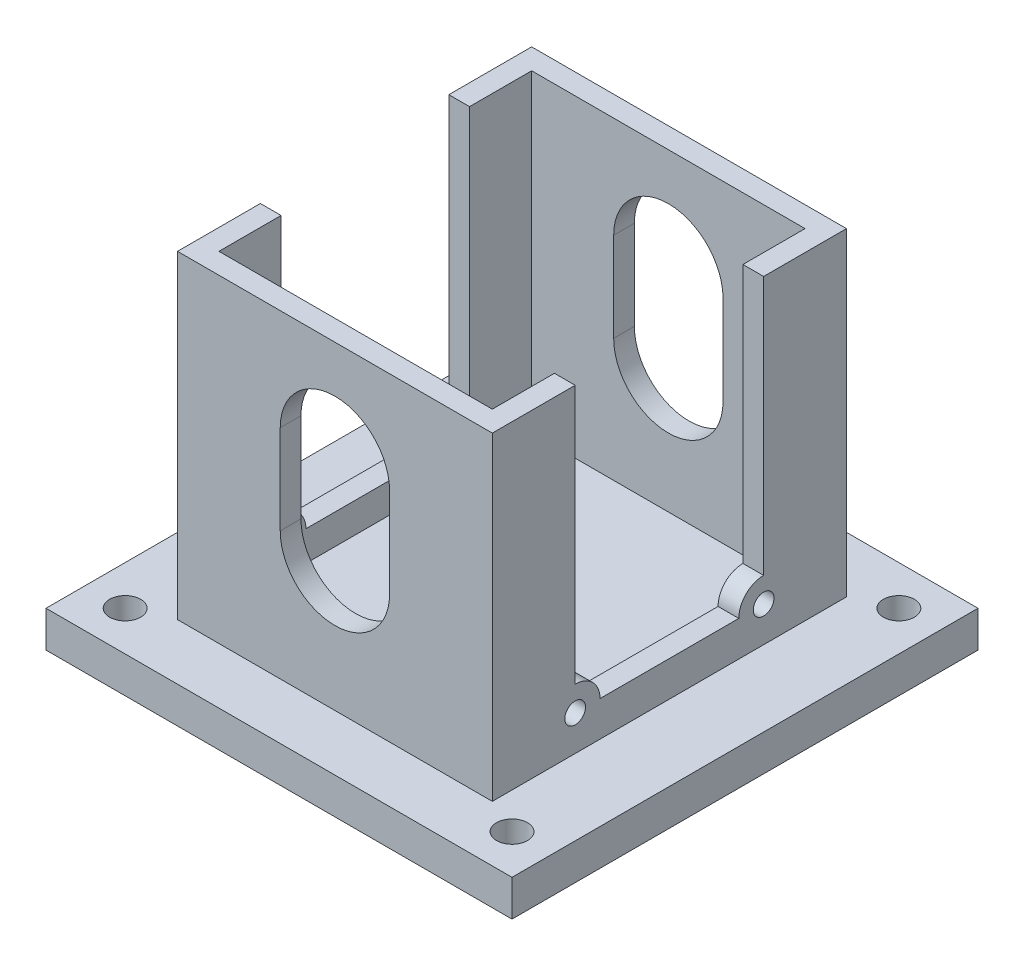
SolidWorks part; units mm, degrees
ref_plane "前视基准面" through (0, 0, 0) normal (0, 0, 1) x (1, 0, 0)
ref_plane "上视基准面" through (0, 0, 0) normal (0, 1, 0) x (1, 0, 0)
ref_plane "右视基准面" through (0, 0, 0) normal (1, 0, 0) x (0, 0, -1)
other "Configuration Table"
sketch "草图1" plane through (0, 0, 0) normal (1, 0, 0) x (0, 0, -1)
  line L0 (0, 0) -> (9.1, 0) construction
  line L1 (0, 0) -> (-9.1, 0) construction
  line L2 (-6.7, 0) -> (6.7, 0)
  line L3 (0, 0) -> (0, 14.2122) construction
  line L4 (-9.1, 0) -> (-10.1, 0) construction
  line L5 (-9.1, 0) -> (-9.1, -1) construction
  line L6 (-9.1, -4.9) -> (9.1, -4.9)
  line L7 (-17.1, 0) -> (-17.1, -4.9)
  line L8 (-17.1, -4.9) -> (-9.1, -4.9)
  line L9 (-9.1, 2.4) -> (-9.1, 27.4)
  line L10 (-9.1, 27.4) -> (-17.1, 27.4)
  line L11 (-17.1, 27.4) -> (-17.1, 0)
  line L12 (-11.5, 0) -> (-17.1, 0) construction
  line L13 (-9.1, -2.4) -> (-9.1, -4.9) construction
  line L14 (9.1, 27.4) -> (17.1, 27.4)
  line L15 (9.1, 2.4) -> (9.1, 27.4)
  line L16 (17.1, 0) -> (17.1, -4.9)
  line L17 (17.1, 27.4) -> (17.1, 0)
  line L18 (17.1, -4.9) -> (9.1, -4.9)
  circle A0 centre (9.1, 0) radius 1
  circle A1 centre (-9.1, 0) radius 1
  arc A2 (-6.7, 0) -> (-9.1, 2.4) centre (-9.1, 0) ccw
  arc A3 (6.7, 0) -> (9.1, 2.4) centre (9.1, 0) cw
  point P26 (0, -4.9)
  dimension "D3" = 2
  dimension "D4" = 2
  dimension "D5" = 4.8
  dimension "D1" = 9.1
  dimension "D6" = 8
  dimension "D7" = 4.9
  dimension "D8" = 25
extrude "凸台-拉伸1" add sketch "草图1" along normal blind 15.2 and the other way blind 15.2
sketch "草图2" plane through (0, 27.4, 0) normal (0, 1, 0) x (1, 0, 0)
  line L0 (-15.2, 17.1) -> (15.2, 17.1) construction
  line L1 (-13.2, 15.1) -> (13.2, 15.1)
  line L2 (-13.2, 15.1) -> (-13.2, -15.1)
  line L3 (-13.2, -15.1) -> (13.2, -15.1)
  line L4 (13.2, 15.1) -> (13.2, -15.1)
  line L5 (15.2, 17.1) -> (15.2, 9.1) construction
  line L6 (-15.2, 17.1) -> (-15.2, 9.1) construction
  line L7 (-15.2, -17.1) -> (15.2, -17.1) construction
  dimension "D1" = 2
  dimension "D2" = 2
  dimension "D3" = 2
  dimension "D4" = 2
extrude "切除-拉伸1" cut sketch "草图2" against normal blind 30.3
sketch "草图3" plane through (0, 0, -17.1) normal (0, 0, -1) x (-1, 0, 0)
  line L0 (0, 17.6091) -> (0, 8.9836) construction
  line L1 (0, 17.6091) -> (0, 8.9836) construction
  line L2 (5.2809, 17.6091) -> (5.2809, 8.9836)
  line L3 (-5.2809, 17.6091) -> (-5.2809, 8.9836)
  arc A0 (5.2809, 17.6091) -> (-5.2809, 17.6091) centre (0, 17.6091) ccw
  arc A1 (-5.2809, 8.9836) -> (5.2809, 8.9836) centre (0, 8.9836) ccw
  point P4 (0, 13.2963)
extrude "切除-拉伸2" cut sketch "草图3" against normal up to surface (34.2 mm away) up to face at (0, 11.25, 17.1)
sketch "草图4" plane through (0, -4.9, 0) normal (0, -1, 0) x (1, 0, 0)
  line L1 (-22.5, 22.5) -> (22.5, 22.5)
  line L2 (-22.5, 22.5) -> (-22.5, -22.5)
  line L3 (-22.5, -22.5) -> (22.5, -22.5)
  line L4 (22.5, 22.5) -> (22.5, -22.5)
  line L5 (-22.5, 22.5) -> (22.5, -22.5) construction
  line L6 (-22.5, -22.5) -> (22.5, 22.5) construction
  point P0 (0, 0)
  dimension "D1" = 45
  dimension "D2" = 45
extrude "凸台-拉伸2" add sketch "草图4" along normal blind 2 and the other way blind 1.5
sketch "草图5" plane through (0, -3.4, 0) normal (0, 1, 0) x (1, 0, 0)
  line L0 (0, 22.5) -> (0, -22.5) construction
  line L1 (-22.5, 22.5) -> (22.5, 22.5) construction
  line L2 (22.5, -22.5) -> (-22.5, -22.5) construction
  line L3 (-22.5, 0) -> (22.5, 0) construction
  line L4 (-22.5, -22.5) -> (-22.5, 22.5) construction
  line L5 (22.5, 22.5) -> (22.5, -22.5) construction
  circle A0 centre (-18.6792, 18.6792) radius 3.8208 construction
  circle A1 centre (-18.6792, 18.6792) radius 1.5
  circle A2 centre (18.6792, 18.6792) radius 3.8208 construction
  circle A3 centre (18.6792, 18.6792) radius 1.5
  circle A4 centre (-18.6792, -18.6792) radius 3.8208 construction
  circle A5 centre (-18.6792, -18.6792) radius 1.5
  circle A6 centre (18.6792, -18.6792) radius 3.8208 construction
  circle A7 centre (18.6792, -18.6792) radius 1.5
  dimension "D1" = 3
extrude "切除-拉伸3" cut sketch "草图5" against normal up to surface (3.5 mm away) up to face at (0, -6.9, 0)
